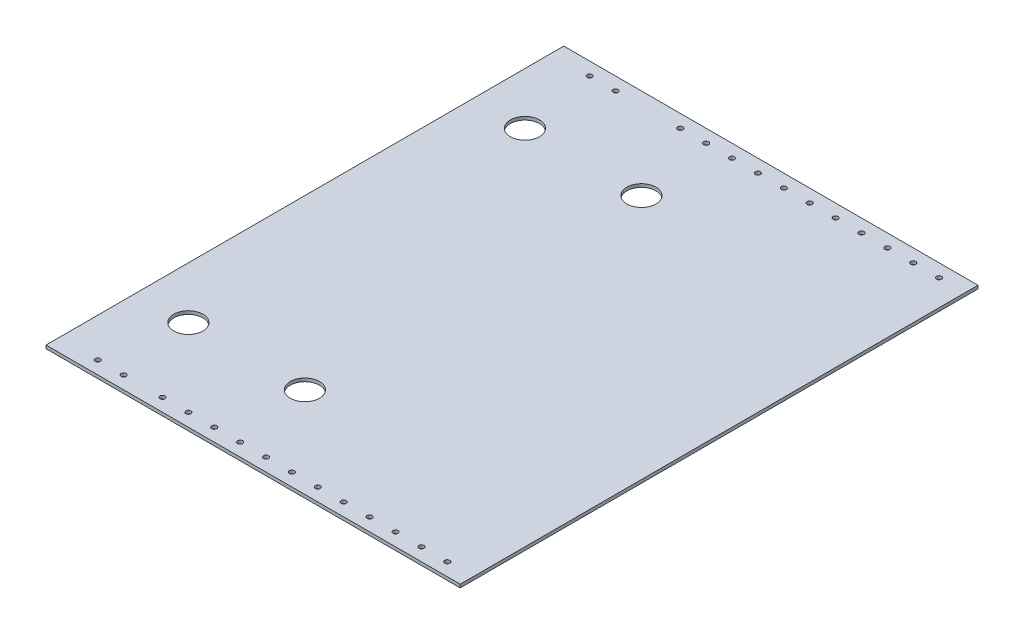
SolidWorks part; units mm, degrees
ref_plane "Front Plane" through (0, 0, 0) normal (0, 0, 1) x (1, 0, 0)
ref_plane "Top Plane" through (0, 0, 0) normal (0, 1, 0) x (1, 0, 0)
ref_plane "Right Plane" through (0, 0, 0) normal (1, 0, 0) x (0, 0, -1)
sketch "Sketch1" plane through (0, 0, 0) normal (0, 1, 0) x (1, 0, 0)
  line L1 (0, 0) -> (406.4, 0)
  line L2 (0, 0) -> (0, 508)
  line L3 (0, 508) -> (406.4, 508)
  line L4 (406.4, 0) -> (406.4, 508)
  dimension "D1" = 406.4
  dimension "D2" = 508
extrude "Boss-Extrude1" add sketch "Sketch1" along normal blind 3.175
sketch "Sketch2" plane through (0, 3.175, 0) normal (0, 1, 0) x (1, 0, 0)
  line L0 (107.95, 419.1) -> (107.95, 508) construction
  line L1 (50.8, 419.1) -> (165.1, 419.1) construction
  line L2 (406.4, 0) -> (406.4, 508) construction
  line L3 (50.8, 88.9) -> (165.1, 88.9) construction
  line L5 (406.4, 508) -> (0, 508) construction
  line L6 (107.95, 88.9) -> (107.95, 0) construction
  line L7 (0, 0) -> (406.4, 0) construction
  circle A0 centre (50.8, 419.1) radius 14.2875
  circle A1 centre (165.1, 419.1) radius 14.2875
  circle A2 centre (50.8, 88.9) radius 14.2875
  circle A3 centre (165.1, 88.9) radius 14.2875
  dimension "D1" = 28.575
  dimension "D2" = 28.575
  dimension "D3" = 28.575
  dimension "D4" = 28.575
  dimension "D5" = 114.3
  dimension "D6" = 114.3
  dimension "D7" = 330.2
  dimension "D9" = 241.3
extrude "Cut-Extrude1" cut sketch "Sketch2" against normal blind 3.175
sketch "Sketch3" plane through (0, 3.175, 0) normal (0, 1, 0) x (1, 0, 0)
  line L0 (0, 12.7) -> (406.4, 12.7) construction
  line L1 (0, 508) -> (0, 0) construction
  line L2 (406.4, 0) -> (406.4, 508) construction
  line L3 (0, 0) -> (406.4, 0) construction
  line L4 (101.6, 0) -> (101.6, 12.7) construction
  line L5 (0, 254) -> (406.4, 254) construction
  line L6 (101.6, 508) -> (101.6, 495.3) construction
  line L7 (0, 495.3) -> (406.4, 495.3) construction
  circle A0 centre (38.1, 12.7) radius 2.4892
  circle A1 centre (63.5, 12.7) radius 2.4892
  circle A2 centre (127, 12.7) radius 2.4892
  circle A3 centre (152.4, 12.7) radius 2.4892
  circle A4 centre (177.8, 12.7) radius 2.4892
  circle A5 centre (203.2, 12.7) radius 2.4892
  circle A6 centre (228.6, 12.7) radius 2.4892
  circle A7 centre (254, 12.7) radius 2.4892
  circle A8 centre (279.4, 12.7) radius 2.4892
  circle A9 centre (304.8, 12.7) radius 2.4892
  circle A10 centre (330.2, 12.7) radius 2.4892
  circle A11 centre (355.6, 12.7) radius 2.4892
  circle A12 centre (381, 12.7) radius 2.4892
  circle A13 centre (381, 495.3) radius 2.4892
  circle A14 centre (355.6, 495.3) radius 2.4892
  circle A15 centre (330.2, 495.3) radius 2.4892
  circle A16 centre (304.8, 495.3) radius 2.4892
  circle A17 centre (279.4, 495.3) radius 2.4892
  circle A18 centre (254, 495.3) radius 2.4892
  circle A19 centre (228.6, 495.3) radius 2.4892
  circle A20 centre (203.2, 495.3) radius 2.4892
  circle A21 centre (177.8, 495.3) radius 2.4892
  circle A22 centre (152.4, 495.3) radius 2.4892
  circle A23 centre (127, 495.3) radius 2.4892
  circle A24 centre (63.5, 495.3) radius 2.4892
  circle A25 centre (38.1, 495.3) radius 2.4892
  circle A27 centre (101.6, 12.7) radius 2.4892
  dimension "D1" = 4.9784
  dimension "D2" = 38.1
  dimension "D4" = 25.4
  dimension "D6" = 25.4
  dimension "D7" = 11
  dimension "D3" = 12.7
  dimension "D5" = 38.1
extrude "Cut-Extrude2" cut sketch "Sketch3" against normal through all both and the other way through all
